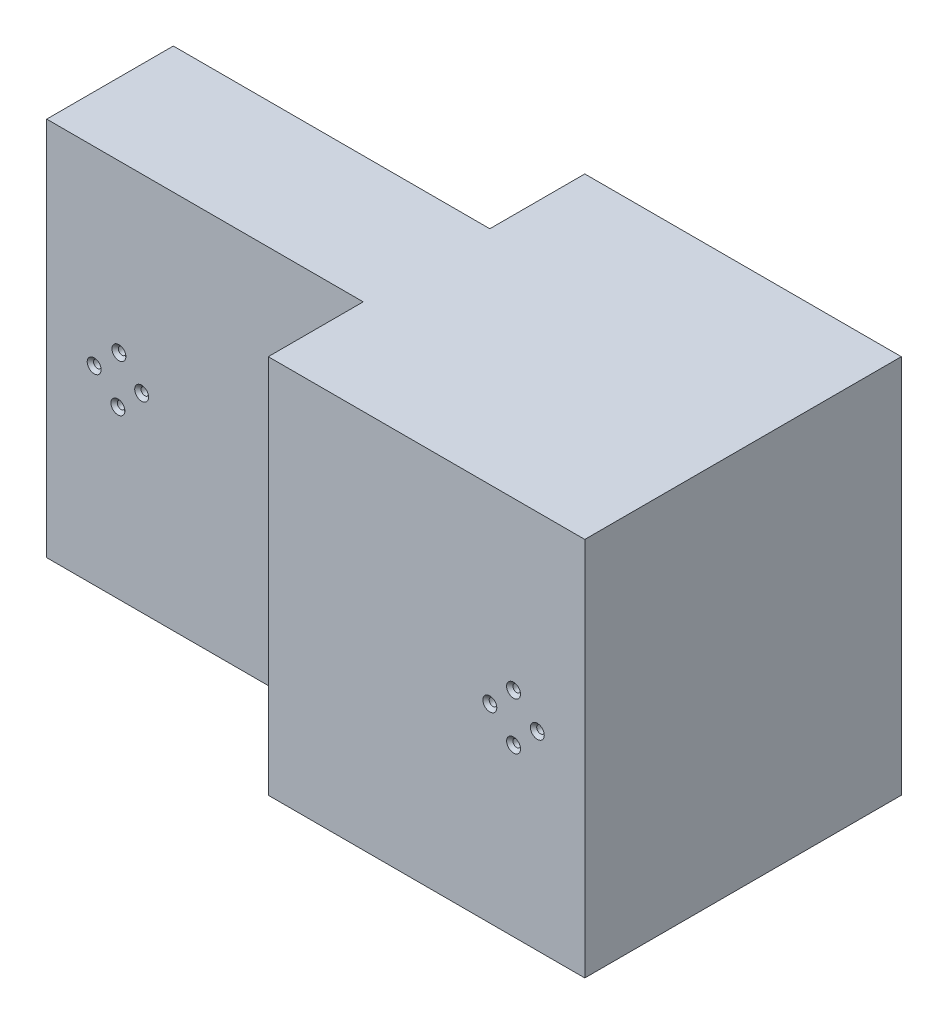
SolidWorks part; units mm, degrees
ref_plane "Front Plane" through (0, 0, 0) normal (0, 0, 1) x (1, 0, 0)
ref_plane "Top Plane" through (0, 0, 0) normal (0, 1, 0) x (1, 0, 0)
ref_plane "Right Plane" through (0, 0, 0) normal (1, 0, 0) x (0, 0, -1)
sketch "Sketch3" plane through (0, 0, 0) normal (0, 1, 0) x (1, 0, 0)
  line L1 (-100, 50) -> (100, 50)
  line L2 (-100, 50) -> (-100, -50)
  line L3 (-100, -50) -> (100, -50)
  line L4 (100, 50) -> (100, -50)
  line L5 (-100, 50) -> (100, -50) construction
  line L6 (-100, -50) -> (100, 50) construction
  point P0 (0, 0)
  dimension "D1" = 200
  dimension "D2" = 100
extrude "Boss-Extrude2" add sketch "Sketch3" along normal blind 120
sketch "Sketch4" plane through (0, 0, 50) normal (0, 0, 1) x (1, 0, 0)
  line L1 (-100, 120) -> (0, 120)
  line L2 (-100, 120) -> (-100, 0)
  line L3 (-100, 0) -> (0, 0)
  line L4 (0, 120) -> (0, 0)
extrude "Cut-Extrude1" cut sketch "Sketch4" against normal blind 30
sketch "Sketch5" plane through (0, 0, -50) normal (0, 0, -1) x (-1, 0, 0)
  line L1 (100, 120) -> (0, 120)
  line L2 (100, 120) -> (100, 0)
  line L3 (100, 0) -> (0, 0)
  line L4 (0, 120) -> (0, 0)
extrude "Cut-Extrude2" cut sketch "Sketch5" against normal blind 30
shell "Shell1" thickness 10
hole_wizard "CSK for M2 Flat Head Machine Screw1" positions "Sketch6" profile "Sketch7" countersink size "M2" standard "ANSI Metric"
sketch "Sketch6" plane through (0, 0, 50) normal (0, 0, 1) x (1, 0, 0)
  line L0 (100, 120) -> (100, 0) construction
  line L1 (0, 0) -> (100, 0) construction
  line L2 (0, 120) -> (100, 120) construction
  point P0 (85, 60)
  point P2 (70, 60)
  point P4 (77.5, 67.5)
  point P6 (77.5, 52.5)
  dimension "D1" = 15
  dimension "D2" = 15
  dimension "D3" = 7.5
  dimension "D4" = 7.5
  dimension "D5" = 15
  dimension "D6" = 52.5
  dimension "D7" = 52.5
sketch "Sketch7" plane through (85, 60, 50) normal (1, 0, 0) x (0, -1, 0)
  line L0 (0, 0) -> (0, 15.721)
  line L1 (0, 15.721) -> (1.2, 15)
  line L2 (1.2, 15) -> (1.2, 1)
  line L3 (1.2, 1) -> (2.2, 0)
  line L5 (2.2, 0) -> (0, 0)
  line L6 (-1.2, 1) -> (-2.2, 0) construction
  line L10 (0, 15.721) -> (-1.2, 15) construction
  line L11 (0, -6.35) -> (0, 107.95) construction
  dimension "Hole Dia." = 2.4
  dimension "Hole Depth" = 15
  dimension "Near C'Sink Dia." = 4.4
  dimension "Near C'Sink Angle" = 90
  dimension "Drill Angle" = 118
hole_wizard "CSK for M2 Flat Head Machine Screw2" positions "Sketch8" profile "Sketch9" countersink size "M2" standard "ANSI Metric"
sketch "Sketch8" plane through (0, 0, 20) normal (0, 0, 1) x (1, 0, 0)
  line L0 (-100, 120) -> (-100, 0) construction
  line L1 (0, 120) -> (-100, 120) construction
  point P0 (-85, 60)
  point P2 (-77.1793, 67.5)
  point P4 (-70, 60)
  point P6 (-77.5, 52.5034)
  dimension "D1" = 15
  dimension "D2" = 15
  dimension "D3" = 7.5
  dimension "D4" = 7.5
  dimension "D5" = 15
  dimension "D6" = 52.5
sketch "Sketch9" plane through (-85, 60, 20) normal (1, 0, 0) x (0, -1, 0)
  line L0 (0, 0) -> (0, 15.721)
  line L1 (0, 15.721) -> (1.2, 15)
  line L2 (1.2, 15) -> (1.2, 1)
  line L3 (1.2, 1) -> (2.2, 0)
  line L5 (2.2, 0) -> (0, 0)
  line L6 (-1.2, 1) -> (-2.2, 0) construction
  line L10 (0, 15.721) -> (-1.2, 15) construction
  line L11 (0, -6.35) -> (0, 107.95) construction
  dimension "Hole Dia." = 2.4
  dimension "Hole Depth" = 15
  dimension "Near C'Sink Dia." = 4.4
  dimension "Near C'Sink Angle" = 90
  dimension "Drill Angle" = 118
